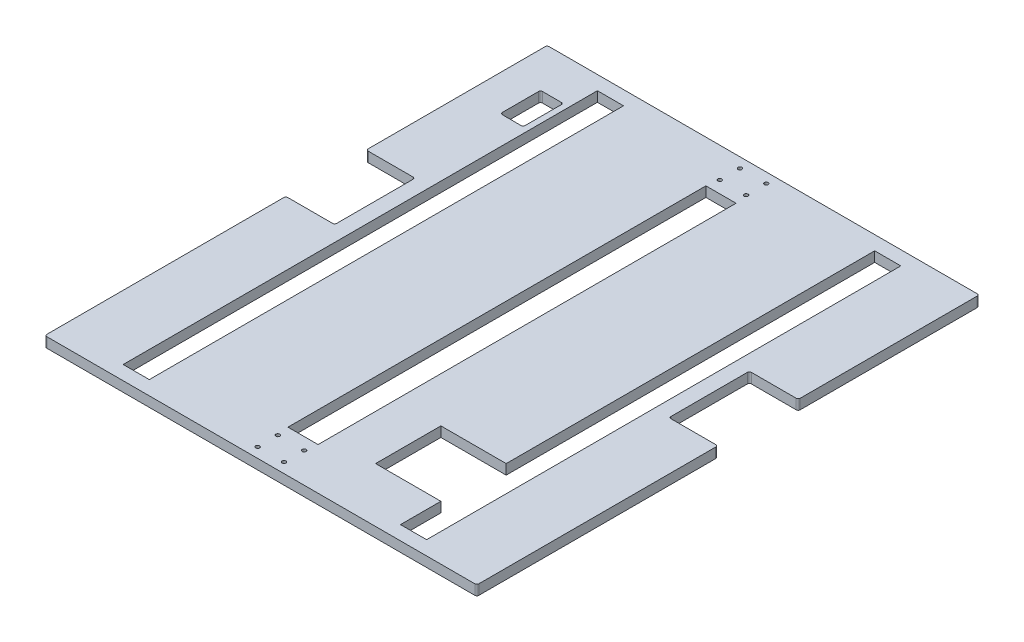
SolidWorks part; units mm, degrees
ref_plane "Front Plane" through (0, 0, 0) normal (0, 0, 1) x (1, 0, 0)
ref_plane "Top Plane" through (0, 0, 0) normal (0, 1, 0) x (1, 0, 0)
ref_plane "Right Plane" through (0, 0, 0) normal (1, 0, 0) x (0, 0, -1)
sketch "Sketch1" plane through (0, 0, 0) normal (0, 1, 0) x (1, 0, 0)
  line L1 (5911.0841, -8452.3124) -> (6341.0841, -8452.3124)
  line L2 (5911.0841, -8452.3124) -> (5911.0841, -8952.3124)
  line L3 (5911.0841, -8952.3124) -> (6341.0841, -8952.3124)
  line L4 (6341.0841, -8452.3124) -> (6341.0841, -8952.3124)
  dimension "D1" = 500
  dimension "D2" = 430
extrude "Boss-Extrude1" add sketch "Sketch1" along normal blind 10
sketch "Sketch2" plane through (0, 10, 0) normal (0, 1, 0) x (1, 0, 0)
  line L0 (5911.0841, -8452.3124) -> (5911.0841, -8952.3124) construction
  line L1 (5959.6841, -8712.448) -> (5911.0841, -8712.448)
  line L2 (5959.6841, -8712.448) -> (5959.6841, -8632.448)
  line L3 (5959.6841, -8632.448) -> (5911.0841, -8632.448)
  line L4 (5911.0841, -8712.448) -> (5911.0841, -8632.448)
  line L9 (6341.0841, -8952.3124) -> (6341.0841, -8452.3124) construction
  line L10 (6341.0841, -8712.448) -> (6292.4841, -8712.448)
  line L11 (6341.0841, -8712.448) -> (6341.0841, -8632.448)
  line L12 (6341.0841, -8632.448) -> (6292.4841, -8632.448)
  line L13 (6292.4841, -8712.448) -> (6292.4841, -8632.448)
  point P12 (6292.4841, -8620.5348)
  point P13 (5959.6841, -8705.9576)
  point P14 (5959.6841, -8712.448)
  point P15 (0, 0)
  dimension "D1" = 48.6
  dimension "D2" = 80
  dimension "D3" = 80
  dimension "D4" = 48.6
extrude "Cut-Extrude1" cut sketch "Sketch2" against normal blind 10
sketch "Sketch3" plane through (0, 10, 0) normal (0, 1, 0) x (1, 0, 0)
  line L0 (5975.0841, -8541.6519) -> (5975.0841, -8938.3124)
  line L1 (6277.0841, -8938.3124) -> (6251.0841, -8938.3124)
  line L2 (6277.0841, -8938.3124) -> (6277.0841, -8466.3124)
  line L3 (6277.0841, -8466.3124) -> (6251.0841, -8466.3124)
  line L4 (6251.0841, -8938.3124) -> (6251.0841, -8466.3124)
  line L5 (5975.0841, -8466.3124) -> (6001.0841, -8466.3124)
  line L11 (5975.0841, -8938.3124) -> (6001.0841, -8938.3124)
  line L12 (6001.0841, -8466.3124) -> (6001.0841, -8938.3124)
  line L33 (5946.4841, -8494.3124) -> (5969.1312, -8494.3124)
  line L34 (5946.4841, -8494.3124) -> (5946.4841, -8534.3124)
  line L35 (5946.4841, -8534.3124) -> (5969.1312, -8534.3124)
  line L36 (5911.0841, -8712.448) -> (5911.0841, -8952.3124) construction
  line L37 (6341.0841, -8952.3124) -> (6341.0841, -8712.448) construction
  line L38 (5969.1312, -8494.3124) -> (5969.1312, -8534.3124)
  line L39 (6111.0841, -8494.3124) -> (6141.0841, -8494.3124)
  line L40 (6111.0841, -8494.3124) -> (6111.0841, -8910.3124)
  line L41 (6111.0841, -8910.3124) -> (6141.0841, -8910.3124)
  line L42 (6141.0841, -8494.3124) -> (6141.0841, -8910.3124)
  line L44 (6341.0841, -8452.3124) -> (5911.0841, -8452.3124) construction
  line L45 (5975.0841, -8466.3124) -> (5975.0841, -8541.6519)
  line L47 (5911.0841, -8952.3124) -> (6341.0841, -8952.3124) construction
  circle A0 centre (6112.9841, -8942.3124) radius 1.9
  circle A1 centre (6139.1841, -8942.3124) radius 1.9
  circle A2 centre (6112.9841, -8462.3124) radius 1.9
  circle A3 centre (6139.1841, -8462.3124) radius 1.9
  circle A4 centre (6112.9841, -8922.3124) radius 1.9
  circle A5 centre (6139.1841, -8922.3124) radius 1.9
  circle A6 centre (6112.9841, -8482.3124) radius 1.9
  circle A7 centre (6139.1841, -8482.3124) radius 1.9
  point P32 (6126.0841, -8452.3124)
  point P33 (6126.0841, -8494.3124)
  dimension "D12" = 10
  dimension "D13" = 10
  dimension "D15" = 42
  dimension "D16" = 20
  dimension "D18" = 20
  dimension "D22" = 42
  dimension "D1" = 26
  dimension "D2" = 472
  dimension "D3" = 26
  dimension "D4" = 472
  dimension "D5" = 10
  dimension "D6" = 64
  dimension "D7" = 40
  dimension "D8" = 64
  dimension "D9" = 30
  dimension "D10" = 416
  dimension "D11" = 110
  dimension "D14" = 10
  dimension "D17" = 20
  dimension "D19" = 20
  dimension "D20" = 14
  dimension "D21" = 14
extrude "Cut-Extrude2" cut sketch "Sketch3" against normal blind 10
sketch "Sketch4" plane through (0, 10, 0) normal (0, 1, 0) x (1, 0, 0)
  line L0 (6251.0841, -8466.3124) -> (6251.0841, -8938.3124) construction
  line L1 (6251.0841, -8898.0965) -> (6186.0841, -8898.0965)
  line L2 (6251.0841, -8898.0965) -> (6251.0841, -8833.0965)
  line L3 (6251.0841, -8833.0965) -> (6186.0841, -8833.0965)
  line L4 (6186.0841, -8898.0965) -> (6186.0841, -8833.0965)
  dimension "D1" = 65
  dimension "D2" = 65
extrude "Cut-Extrude3" cut sketch "Sketch4" against normal blind 10
fillet "Fillet2" radius 2 16 edges at (5969.1312, 5, 8494.3124) (5969.1312, 5, 8534.3124) (5946.4841, 5, 8534.3124) (5946.4841, 5, 8494.3124) (6292.4841, 5, 8632.448) (6341.0841, 5, 8632.448) (6341.0841, 5, 8712.448) (6292.4841, 5, 8712.448) (5959.6841, 5, 8632.448) (5959.6841, 5, 8712.448) (5911.0841, 5, 8712.448) (5911.0841, 5, 8632.448) (5911.0841, 5, 8452.3124) (6341.0841, 5, 8452.3124) (6341.0841, 5, 8952.3124) (5911.0841, 5, 8952.3124)
ref_plane "Plane1" through (6126.0841, 0, 0) normal (-1, 0, 0) x (0, 0, 1)
sketch "Sketch5" plane through (6126.0841, 0, 0) normal (-1, 0, 0) x (0, 0, 1)
  line L1 (8395.6862, 142.8464) -> (9031.9061, 142.8464)
  line L2 (8395.6862, 142.8464) -> (8395.6862, -229.0644)
  line L3 (8395.6862, -229.0644) -> (9031.9061, -229.0644)
  line L4 (9031.9061, 142.8464) -> (9031.9061, -229.0644)
